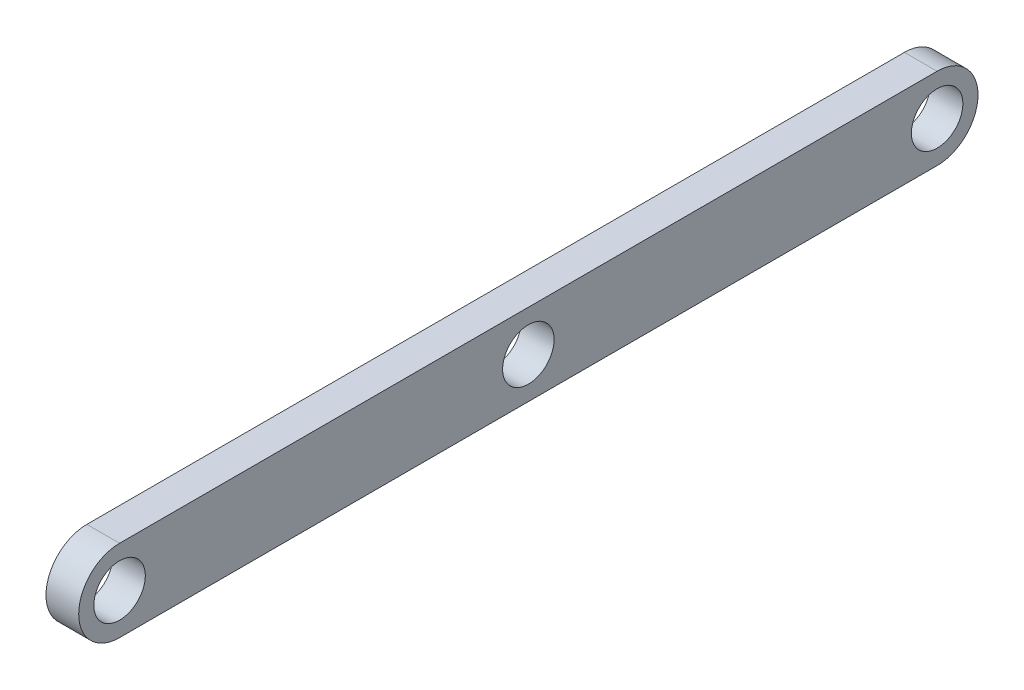
SolidWorks part; units mm, degrees
ref_plane "Front Plane" through (0, 0, 0) normal (0, 0, 1) x (1, 0, 0)
ref_plane "Top Plane" through (0, 0, 0) normal (0, 1, 0) x (1, 0, 0)
ref_plane "Right Plane" through (0, 0, 0) normal (1, 0, 0) x (0, 0, -1)
sketch "Sketch1" plane through (0, 0, 0) normal (1, 0, 0) x (0, 0, -1)
  line L0 (-77.47, 8.4137) -> (49.53, 8.4137)
  line L2 (49.53, -4.2862) -> (-77.47, -4.2863)
  arc A0 (-77.47, -4.2863) -> (-77.47, 8.4137) centre (-77.47, 2.0637) cw
  arc A1 (49.53, -4.2862) -> (49.53, 8.4137) centre (49.53, 2.0637) ccw
  dimension "D1" = 12.7
  dimension "D2" = 127
extrude "Boss-Extrude1" add sketch "Sketch1" along normal blind 5.08
hole_wizard "Ø8.0mm Dowel Hole1" positions "Sketch4" profile "Sketch3" hole size "Ø8.0" standard "ANSI Metric" end condition through all
sketch "Sketch4" plane through (5.08, 0, 0) normal (1, 0, 0) x (0, 0, -1)
  line L1 (-13.97, 8.4137) -> (-13.97, -4.2863) construction
  line L2 (49.53, 8.4137) -> (-77.47, 8.4137) construction
  line L3 (-77.47, -4.2863) -> (49.53, -4.2862) construction
  arc A0 (-77.47, 8.4137) -> (-77.47, -4.2863) centre (-77.47, 2.0637) ccw construction
  arc A1 (49.53, -4.2862) -> (49.53, 8.4137) centre (49.53, 2.0637) ccw construction
  point P0 (-77.47, 2.0637)
  point P2 (49.53, 2.0637)
  point P12 (-13.97, 2.0637)
  point P22 (0, 0)
sketch "Sketch3" plane through (5.08, 2.0637, 77.47) normal (0, 1, 0) x (0, 0, -1)
  line L0 (0, 0) -> (0, 5.08)
  line L1 (0, 5.08) -> (4, 5.08)
  line L2 (4, 5.08) -> (4, 0)
  line L5 (4, 0) -> (0, 0)
  line L11 (0, -6.35) -> (0, 107.95) construction
  dimension "Thru Hole Dia." = 8
  dimension "Thru Hole Depth" = 5.08
sketch "Sketch5" plane through (0, 8.4137, 0) normal (0, 1, 0) x (1, 0, 0)
  line L0 (5.08, -13.97) -> (0, -13.97) construction
  line L1 (0, -64.77) -> (5.08, -64.77)
  line L2 (0, -64.77) -> (0, 36.83)
  line L3 (0, 36.83) -> (5.08, 36.83)
  line L4 (5.08, -64.77) -> (5.08, 36.83)
  line L5 (5.08, 49.53) -> (5.08, -77.47) construction
  line L6 (0, 49.53) -> (0, -77.47) construction
  line L7 (2.54, -64.77) -> (2.54, 36.83) construction
  point P10 (5.08, -13.97)
  dimension "D1" = 5.08
  dimension "D2" = 101.6
